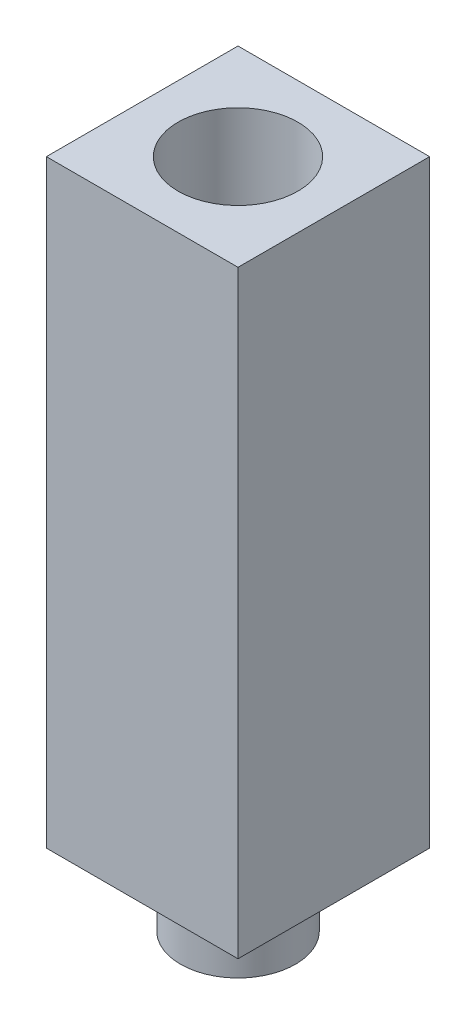
SolidWorks part; units mm, degrees
ref_plane "Plan de face" through (0, 0, 0) normal (0, 0, 1) x (1, 0, 0)
ref_plane "Plan de dessus" through (0, 0, 0) normal (0, 1, 0) x (1, 0, 0)
ref_plane "Plan de droite" through (0, 0, 0) normal (1, 0, 0) x (0, 0, -1)
sketch "Sketch1" plane through (0, 0, 0) normal (0, 1, 0) x (1, 0, 0)
  circle A0 centre (0, 0) radius 2.4
  dimension "D1" = 4.8
extrude "Boss-Extrude1" add sketch "Sketch1" along normal blind 3
sketch "Sketch2" plane through (0, 3, 0) normal (0, 1, 0) x (1, 0, 0)
  line L1 (-4, -4) -> (4, -4)
  line L2 (-4, -4) -> (-4, 4)
  line L3 (-4, 4) -> (4, 4)
  line L4 (4, -4) -> (4, 4)
  line L5 (-4, -4) -> (4, 4) construction
  line L6 (-4, 4) -> (4, -4) construction
  point P0 (0, 0)
  point P6 (0, 0)
  dimension "D1" = 8
  dimension "D2" = 8
extrude "Boss-Extrude2" add sketch "Sketch2" along normal blind 25
sketch "Sketch3" plane through (0, 28, 0) normal (0, 1, 0) x (1, 0, 0)
  circle A2 centre (0, 0) radius 2.5
  dimension "D1" = 5
extrude "Cut-Extrude1" cut sketch "Sketch3" against normal blind 4
equation "\"D2@Sketch2\"=\"D1@Sketch2\""
